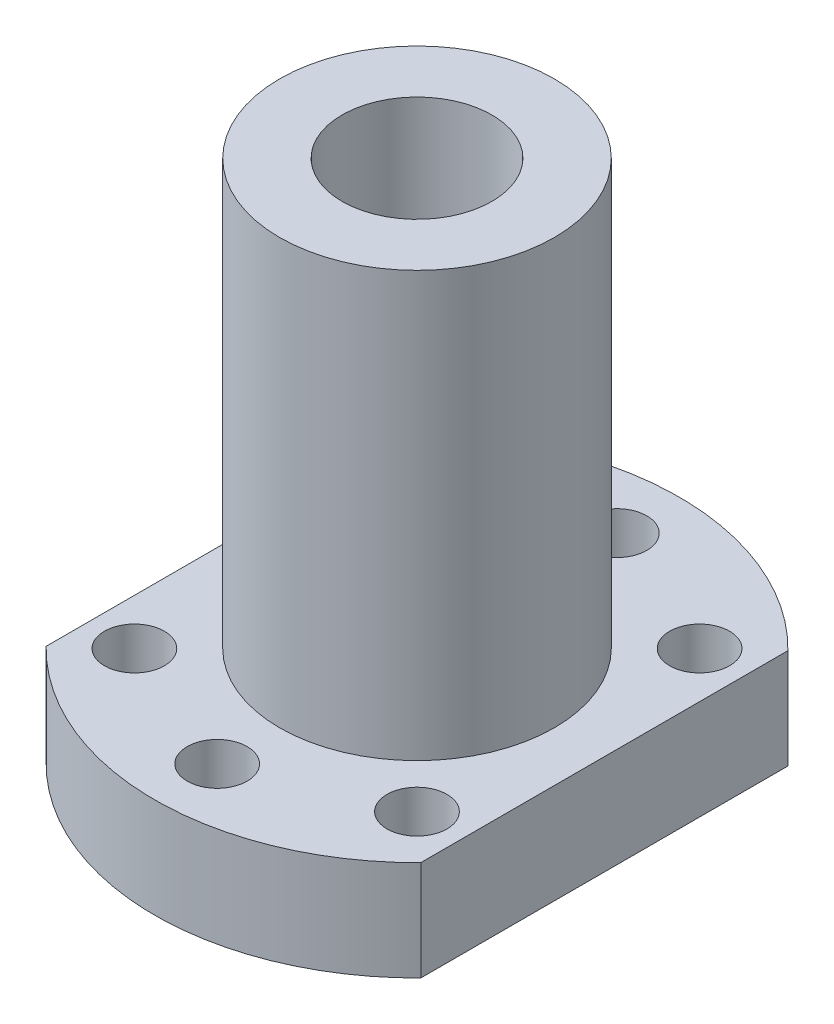
SolidWorks part; units mm, degrees
material "不锈钢 (铁素体)"
ref_plane "前视基准面" through (0, 0, 0) normal (0, 0, 1) x (1, 0, 0)
ref_plane "上视基准面" through (0, 0, 0) normal (0, 1, 0) x (1, 0, 0)
ref_plane "右视基准面" through (0, 0, 0) normal (1, 0, 0) x (0, 0, -1)
sketch "草图1" plane through (0, 0, 0) normal (0, 1, 0) x (1, 0, 0)
  line L0 (0, 31.2311) -> (0, -30.3147) construction
  line L1 (-42.0581, 0) -> (42.8284, 0) construction
  line L2 (-15, 14.6969) -> (-15, -14.6969)
  line L3 (15, 14.6969) -> (15, -14.6969)
  circle A0 centre (0, 0) radius 6
  circle A1 centre (0, 0) radius 11
  arc A2 (-15, -14.6969) -> (15, -14.6969) centre (0, 0) ccw
  circle A3 centre (0, 0) radius 16 construction
  arc A4 (15, 14.6969) -> (-15, 14.6969) centre (0, 0) ccw
  circle A5 centre (0, -16) radius 2.4
  circle A6 centre (-11.3137, -11.3137) radius 2.4
  circle A7 centre (11.3137, -11.3137) radius 2.4
  circle A8 centre (11.3137, 11.3137) radius 2.4
  circle A9 centre (0, 16) radius 2.4
  circle A10 centre (-11.3137, 11.3137) radius 2.4
  dimension "D1" = 12
  dimension "D2" = 22
  dimension "D3" = 42
  dimension "D4" = 32
  dimension "D6" = 4.8
  dimension "D5" = 30
  dimension "D7" = 90
extrude "凸台-拉伸1" add sketch "草图1" along normal blind 8 contours L3 A4 L2 A2 A9 A8 A1 A5 A6 A7 A10 region at (0, 0, -20.4839)
extrude "凸台-拉伸2" add sketch "草图1<3>" along normal blind 42 contours A1 A0 region at (-10.6889, 0, 0)
sketch "草图1<3>" plane through (0, 0, 0) normal (0, 1, 0) x (1, 0, 0) same geometry as "草图1"
sketch "草图2" plane through (-15, 0, 0) normal (-1, 0, 0) x (0, 0, 1)
  line L0 (0, 0) -> (0, 8) construction
  line L1 (-14.6969, 8) -> (14.6969, 8) construction
  line L3 (-14.6969, 8) -> (-14.6969, 0) construction
  line L4 (-14.6969, 4) -> (14.6969, 4) construction
  line L5 (14.6969, 8) -> (14.6969, 0) construction
  circle A0 centre (0, 4) radius 3
  dimension "D1" = 6
extrude "切除-拉伸1" cut sketch "草图2" against normal blind 20
